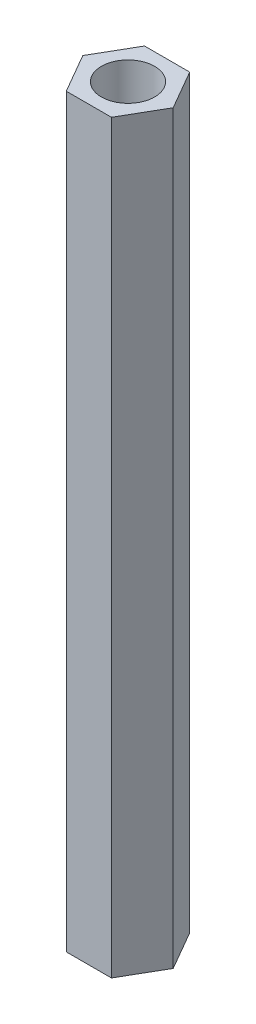
SolidWorks part; units mm, degrees
material "黄铜"
ref_plane "前视基准面" through (0, 0, 0) normal (0, 0, 1) x (1, 0, 0)
ref_plane "上视基准面" through (0, 0, 0) normal (0, 1, 0) x (1, 0, 0)
ref_plane "右视基准面" through (0, 0, 0) normal (1, 0, 0) x (0, 0, -1)
other "Configuration Table"
ref_axis "基准轴1" through (-88.99, 0, 0) along (1, 0, 0)
ref_axis "基准轴2" through (0, 66, 0) along (0, -1, 0)
ref_axis "基准轴3" through (0, 0, -88.99) along (0, 0, 1)
sketch "草图1" plane through (0, 0, 0) normal (0, 1, 0) x (1, 0, 0)
  line L1 (0.8487, 1.47) -> (-0.8487, 1.47)
  line L2 (-0.8487, 1.47) -> (-1.6974, 0)
  line L3 (-1.6974, 0) -> (-0.8487, -1.47)
  line L4 (-0.8487, -1.47) -> (0.8487, -1.47)
  line L5 (0.8487, -1.47) -> (1.6974, 0)
  line L6 (1.6974, 0) -> (0.8487, 1.47)
  circle A0 centre (0, 0) radius 1
  circle A1 centre (0, 0) radius 1.47 construction
  dimension "D1" = 1
  dimension "D2" = 2.94
extrude "凸台-拉伸1" add sketch "草图1" along normal blind 28
